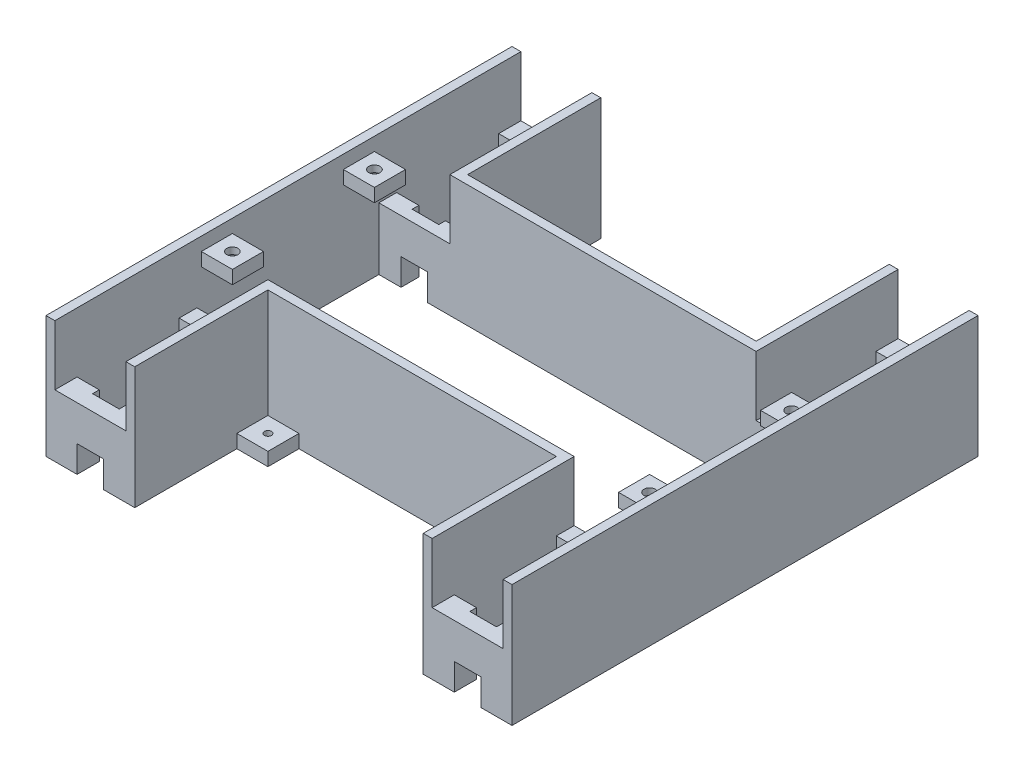
SolidWorks part; units mm, degrees
ref_plane "前视基准面" through (0, 0, 0) normal (0, 0, 1) x (1, 0, 0)
ref_plane "上视基准面" through (0, 0, 0) normal (0, 1, 0) x (1, 0, 0)
ref_plane "右视基准面" through (0, 0, 0) normal (1, 0, 0) x (0, 0, -1)
other "Configuration Table"
sketch "草图1" plane through (0, 0, 0) normal (0, 1, 0) x (1, 0, 0)
  line L1 (0, 20.5) -> (101, 20.5)
  line L2 (0, 20.5) -> (0, -20.5)
  line L3 (0, -20.5) -> (101, -20.5)
  line L4 (101, 20.5) -> (101, -20.5)
  line L5 (0, 52.5) -> (16, 52.5)
  line L6 (0, 52.5) -> (0, 20.5)
  line L7 (0, 20.5) -> (16, 20.5)
  line L8 (16, 52.5) -> (16, 20.5)
  line L9 (101, 20.5) -> (85, 20.5)
  line L10 (101, 20.5) -> (101, 52.5)
  line L11 (101, 52.5) -> (85, 52.5)
  line L12 (85, 20.5) -> (85, 52.5)
  line L13 (101, -52.5) -> (85, -52.5)
  line L14 (101, -52.5) -> (101, -20.5)
  line L15 (101, -20.5) -> (85, -20.5)
  line L16 (85, -52.5) -> (85, -20.5)
  line L17 (0, -20.5) -> (16, -20.5)
  line L18 (0, -20.5) -> (0, -52.5)
  line L19 (0, -52.5) -> (16, -52.5)
  line L20 (16, -20.5) -> (16, -52.5)
  line L21 (0, 52.5) -> (-2, 52.5)
  line L22 (0, 52.5) -> (0, -52.5)
  line L23 (0, -52.5) -> (-2, -52.5)
  line L24 (-2, 52.5) -> (-2, -52.5)
  line L25 (101, 52.5) -> (103, 52.5)
  line L26 (101, 52.5) -> (101, -52.5)
  line L27 (101, -52.5) -> (103, -52.5)
  line L28 (103, 52.5) -> (103, -52.5)
  line L29 (103, 52.5) -> (83, 52.5)
  line L30 (103, 52.5) -> (103, 54.5)
  line L31 (103, 54.5) -> (83, 54.5)
  line L32 (83, 52.5) -> (83, 54.5)
  line L33 (103, -52.5) -> (83, -52.5)
  line L34 (103, -52.5) -> (103, -54.5)
  line L35 (103, -54.5) -> (83, -54.5)
  line L36 (83, -52.5) -> (83, -54.5)
  line L37 (-2, 52.5) -> (18, 52.5)
  line L38 (-2, 52.5) -> (-2, 54.5)
  line L39 (-2, 54.5) -> (18, 54.5)
  line L40 (18, 52.5) -> (18, 54.5)
  line L41 (-2, -52.5) -> (18, -52.5)
  line L42 (-2, -52.5) -> (-2, -54.5)
  line L43 (-2, -54.5) -> (18, -54.5)
  line L44 (18, -52.5) -> (18, -54.5)
  line L45 (18, 52.5) -> (16, 52.5)
  line L46 (18, 52.5) -> (18, 20.5)
  line L47 (18, 20.5) -> (16, 20.5)
  line L48 (16, 52.5) -> (16, 20.5)
  line L49 (83, 52.5) -> (85, 52.5)
  line L50 (83, 52.5) -> (83, 20.5)
  line L51 (83, 20.5) -> (85, 20.5)
  line L52 (85, 52.5) -> (85, 20.5)
  line L53 (18, -52.5) -> (16, -52.5)
  line L54 (18, -52.5) -> (18, -20.5)
  line L55 (18, -20.5) -> (16, -20.5)
  line L56 (16, -52.5) -> (16, -20.5)
  line L57 (83, -52.5) -> (85, -52.5)
  line L58 (83, -52.5) -> (83, -20.5)
  line L59 (83, -20.5) -> (85, -20.5)
  line L60 (85, -52.5) -> (85, -20.5)
  line L61 (18, -20.5) -> (83, -20.5)
  line L62 (18, -20.5) -> (18, -22.5)
  line L63 (18, -22.5) -> (83, -22.5)
  line L64 (83, -20.5) -> (83, -22.5)
  line L65 (18, 20.5) -> (83, 20.5)
  line L66 (18, 20.5) -> (18, 22.5)
  line L67 (18, 22.5) -> (83, 22.5)
  line L68 (83, 20.5) -> (83, 22.5)
  point P4 (0, 0)
  dimension "D1" = 101
  dimension "D2" = 41
  dimension "D3" = 32
  dimension "D4" = 16
  dimension "D6" = 2
extrude "凸台-拉伸2" add sketch "草图1" along normal blind 27.5 contours L21 L24 L23 L18 L2 L6 | L37 L40 L39 L38 L21 L5 | L46 L37 L8 L1 | L67 L46 L1 L50 | L29 L50 L1 L12 | L32 L29 L11 L25 L30 L31 | L28 L25 L10 L4 L14 L27 | L33 L36 L35 L34 L27 L13 | L58 L33 L16 L3 | L54 L63 L58 L3 | L41 L54 L3 L20 | L44 L41 L19 L23 L42 L43 region at (-1, 0, 0) region at (17, 0, -36.5) region at (8, 0, -53.5) region at (50.5, 0, -21.5) region at (17, 0, 36.5) region at (8, 0, 53.5) region at (84, 0, -36.5) region at (50.5, 0, 21.5) region at (84, 0, 36.5) region at (102, 0, 0) region at (93, 0, -53.5) region at (93, 0, 53.5)
sketch "草图2" plane through (0, 0, 0) normal (0, -1, 0) x (1, 0, 0)
  line L0 (0, -52.5) -> (0, 52.5) construction
  line L1 (16, 52.5) -> (0, 52.5)
  line L2 (16, 52.5) -> (16, 47.5)
  line L3 (16, 47.5) -> (0, 47.5)
  line L4 (0, 52.5) -> (0, 47.5)
  line L5 (103, -54.5) -> (103, 54.5) construction
  line L6 (-2, 54.5) -> (103, 54.5)
  line L7 (-2, 54.5) -> (-2, 52.5)
  line L8 (-2, 52.5) -> (103, 52.5)
  line L9 (103, 54.5) -> (103, 52.5)
  line L10 (101, 52.5) -> (101, -52.5) construction
  line L11 (85, 52.5) -> (101, 52.5)
  line L12 (85, 52.5) -> (85, 47.5)
  line L13 (85, 47.5) -> (101, 47.5)
  line L14 (101, 52.5) -> (101, 47.5)
  line L16 (16, -52.5) -> (0, -52.5)
  line L17 (16, -52.5) -> (16, -47.5)
  line L18 (16, -47.5) -> (0, -47.5)
  line L19 (0, -52.5) -> (0, -47.5)
  line L20 (85, -52.5) -> (101, -52.5)
  line L21 (85, -52.5) -> (85, -47.5)
  line L22 (85, -47.5) -> (101, -47.5)
  line L23 (101, -52.5) -> (101, -47.5)
  line L24 (-2, -54.5) -> (103, -54.5)
  line L25 (-2, -54.5) -> (-2, -52.5)
  line L26 (-2, -52.5) -> (103, -52.5)
  line L27 (103, -54.5) -> (103, -52.5)
  line L28 (16, 20.5) -> (0, 20.5)
  line L29 (16, 20.5) -> (16, 24.5)
  line L30 (16, 24.5) -> (0, 24.5)
  line L31 (0, 20.5) -> (0, 24.5)
  line L32 (85, 20.5) -> (101, 20.5)
  line L33 (85, 20.5) -> (85, 24.5)
  line L34 (85, 24.5) -> (101, 24.5)
  line L35 (101, 20.5) -> (101, 24.5)
  line L36 (85, -20.5) -> (101, -20.5)
  line L37 (85, -20.5) -> (85, -24.5)
  line L38 (85, -24.5) -> (101, -24.5)
  line L39 (101, -20.5) -> (101, -24.5)
  line L40 (16, -20.5) -> (0, -20.5)
  line L41 (16, -20.5) -> (16, -24.5)
  line L42 (16, -24.5) -> (0, -24.5)
  line L43 (0, -20.5) -> (0, -24.5)
  dimension "D1" = 5
  dimension "D2" = 4
extrude "凸台-拉伸3" add sketch "草图2" against normal blind 14 contours L13 L14 L11 L12 | L3 L4 L1 L2 | L16 L19 L18 L17 | L20 L23 L22 L21 | L28 L31 L30 L29 | L32 L35 L34 L33 | L42 L43 L40 L41 | L38 L39 L36 L37
extrude "切除-拉伸1" cut sketch "草图2<3>" against normal through all contours L24 L27 L26 L25 | L6 L9 L8 L7
sketch "草图2<3>" plane through (0, 0, 0) normal (0, -1, 0) x (1, 0, 0) same geometry as "草图2"
sketch "草图3" plane through (0, 0, 0) normal (0, -1, 0) x (1, 0, 0)
  line L0 (101, 20.5) -> (101, -20.5) construction
  line L1 (0, 19.5) -> (7, 19.5)
  line L2 (0, 19.5) -> (0, 12.5)
  line L3 (0, 12.5) -> (7, 12.5)
  line L4 (7, 19.5) -> (7, 12.5)
  line L5 (0, -19.5) -> (7, -19.5)
  line L6 (0, -19.5) -> (0, -12.5)
  line L7 (0, -12.5) -> (7, -12.5)
  line L8 (7, -19.5) -> (7, -12.5)
  line L9 (101, 19.5) -> (94, 19.5)
  line L10 (101, 19.5) -> (101, 12.5)
  line L11 (101, 12.5) -> (94, 12.5)
  line L12 (94, 19.5) -> (94, 12.5)
  line L13 (101, -19.5) -> (94, -19.5)
  line L14 (101, -19.5) -> (101, -12.5)
  line L15 (101, -12.5) -> (94, -12.5)
  line L16 (94, -19.5) -> (94, -12.5)
  line L17 (0, -20.5) -> (0, 20.5) construction
  line L18 (0, 20.5) -> (101, 20.5) construction
  line L19 (0, -20.5) -> (101, -20.5) construction
  line L20 (0, 19.5) -> (7, 12.5) construction
  line L21 (0, -12.5) -> (7, -19.5) construction
  line L22 (94, -12.5) -> (101, -19.5) construction
  line L23 (94, 19.5) -> (101, 12.5) construction
  circle A0 centre (3.5, 16) radius 2
  circle A1 centre (3.5, 16) radius 1.25
  circle A2 centre (97.5, 16) radius 2
  circle A3 centre (97.5, 16) radius 1.25
  circle A4 centre (97.5, -16) radius 2
  circle A5 centre (97.5, -16) radius 1.25
  circle A8 centre (3.5, -16) radius 1.25
  circle A9 centre (3.5, -16) radius 2
  dimension "D4" = 2.5
  dimension "D5" = 4
  dimension "D1" = 7
  dimension "D2" = 1
  dimension "D3" = 1
extrude "凸台-拉伸4" add sketch "草图3" along normal blind 3 from offset 24.5 separate body contours L8 L7 L6 L5 | L4 L3 L2 L1 | L12 L11 L10 L9 | L15 L16 L13 L14 | A1 | A3 | A5 | A8 offset against normal yes
extrude "切除-拉伸3" cut sketch "草图3<4>" against normal blind 1.5 from surface contours A0 | A9 | A2 | A4 starting at face at (3.5, 21.5, 16)
sketch "草图3<4>" plane through (0, 0, 0) normal (0, -1, 0) x (1, 0, 0) same geometry as "草图3"
sketch "草图4" plane through (0, 0, 0) normal (0, -1, 0) x (1, 0, 0)
  line L0 (18, 22.5) -> (83, 22.5) construction
  line L1 (18, 29.5) -> (25, 29.5)
  line L2 (18, 29.5) -> (18, 22.5)
  line L3 (18, 22.5) -> (25, 22.5)
  line L4 (25, 29.5) -> (25, 22.5)
  line L5 (18, -22.5) -> (83, -22.5) construction
  line L6 (83, 29.5) -> (76, 29.5)
  line L7 (83, 29.5) -> (83, 22.5)
  line L8 (83, 22.5) -> (76, 22.5)
  line L9 (76, 29.5) -> (76, 22.5)
  line L10 (18, -29.5) -> (25, -29.5)
  line L11 (18, -29.5) -> (18, -22.5)
  line L12 (18, -22.5) -> (25, -22.5)
  line L13 (25, -29.5) -> (25, -22.5)
  line L15 (83, -29.5) -> (76, -29.5)
  line L16 (83, -29.5) -> (83, -22.5)
  line L17 (83, -22.5) -> (76, -22.5)
  line L18 (76, -29.5) -> (76, -22.5)
  line L19 (18, -22.5) -> (18, -52.5) construction
  line L20 (83, 52.5) -> (83, 22.5) construction
  line L21 (18, 29.5) -> (25, 22.5) construction
  line L22 (83, 29.5) -> (76, 22.5) construction
  line L23 (25, -29.5) -> (18, -22.5) construction
  line L24 (83, -29.5) -> (76, -22.5) construction
  circle A0 centre (21.5, 26) radius 0.8
  circle A1 centre (79.5, 26) radius 0.8
  circle A2 centre (79.5, -26) radius 0.8
  circle A3 centre (21.5, -26) radius 0.8
  dimension "D1" = 1.6
  dimension "D2" = 7
  dimension "D3" = 7
extrude "凸台-拉伸5" add sketch "草图4" against normal blind 3 separate body contours L10 L13 L12 L11 | A3 | L1 L4 L3 L2 | A0 | L6 L9 L8 L7 | A1 | L15 L18 L17 L16 | A2
sketch "草图5" plane through (0, 0, 52.5) normal (0, 0, 1) x (1, 0, 0)
  line L5 (-2, 0) -> (18, 0) construction
  line L6 (5, 0) -> (11, 0)
  line L7 (5, 0) -> (5, 6)
  line L8 (5, 6) -> (11, 6)
  line L9 (11, 0) -> (11, 6)
  line L10 (83, 0) -> (103, 0) construction
  line L11 (90, 0) -> (96, 0)
  line L12 (90, 0) -> (90, 6)
  line L13 (90, 6) -> (96, 6)
  line L14 (96, 0) -> (96, 6)
  line L15 (-2, 27.5) -> (-2, 0) construction
  line L16 (18, 0) -> (18, 27.5) construction
  line L17 (83, 27.5) -> (83, 0) construction
  line L18 (103, 27.5) -> (103, 0) construction
  dimension "D1" = 7
  dimension "D2" = 7
  dimension "D3" = 7
  dimension "D4" = 7
  dimension "D5" = 6
extrude "切除-拉伸4" cut sketch "草图5" against normal through all
sketch "草图6" plane through (0, 6, 0) normal (0, -1, 0) x (1, 0, 0)
  line L0 (5, 47.5) -> (5, 52.5) construction
  line L1 (5, 49) -> (11, 49)
  line L2 (5, 49) -> (5, 47.5)
  line L3 (5, 47.5) -> (11, 47.5)
  line L4 (11, 49) -> (11, 47.5)
  line L6 (5, 20.5) -> (5, 24.5) construction
  line L7 (5, 24.5) -> (11, 24.5)
  line L8 (5, 24.5) -> (5, 23)
  line L9 (5, 23) -> (11, 23)
  line L10 (11, 24.5) -> (11, 23)
  line L11 (11, 24.5) -> (5, 24.5) construction
  line L13 (11, 20.5) -> (11, 24.5) construction
  line L14 (96, 20.5) -> (96, 24.5) construction
  line L15 (90, 24.5) -> (96, 24.5)
  line L16 (90, 24.5) -> (90, 23)
  line L17 (90, 23) -> (96, 23)
  line L18 (96, 24.5) -> (96, 23)
  line L19 (96, 47.5) -> (96, 52.5) construction
  line L20 (90, 47.5) -> (96, 47.5)
  line L21 (90, 47.5) -> (90, 49)
  line L22 (90, 49) -> (96, 49)
  line L23 (96, 47.5) -> (96, 49)
  line L24 (96, -24.5) -> (96, -20.5) construction
  line L25 (90, -24.5) -> (96, -24.5)
  line L26 (90, -24.5) -> (90, -23)
  line L27 (90, -23) -> (96, -23)
  line L28 (96, -24.5) -> (96, -23)
  line L29 (96, -52.5) -> (96, -47.5) construction
  line L30 (90, -47.5) -> (96, -47.5)
  line L31 (90, -47.5) -> (90, -49)
  line L32 (90, -49) -> (96, -49)
  line L33 (96, -47.5) -> (96, -49)
  line L34 (5, -52.5) -> (5, -47.5) construction
  line L35 (11, -47.5) -> (5, -47.5)
  line L36 (11, -47.5) -> (11, -49)
  line L37 (11, -49) -> (5, -49)
  line L38 (5, -47.5) -> (5, -49)
  line L39 (11, -24.5) -> (11, -20.5) construction
  line L40 (5, -24.5) -> (11, -24.5)
  line L41 (5, -24.5) -> (5, -23)
  line L42 (5, -23) -> (11, -23)
  line L43 (11, -24.5) -> (11, -23)
  point P6 (0, 0)
  point P60 (90, -23.75)
  dimension "D1" = 1.5
extrude "切除-拉伸5" cut sketch "草图6" against normal through all contours L3 L4 L1 L2 | L9 L10 L7 L8 | L40 L43 L42 L41 | L37 L38 L35 L36 | L32 L33 L30 L31 | L25 L28 L27 L26 | L17 L18 L15 L16 | L20 L23 L22 L21
